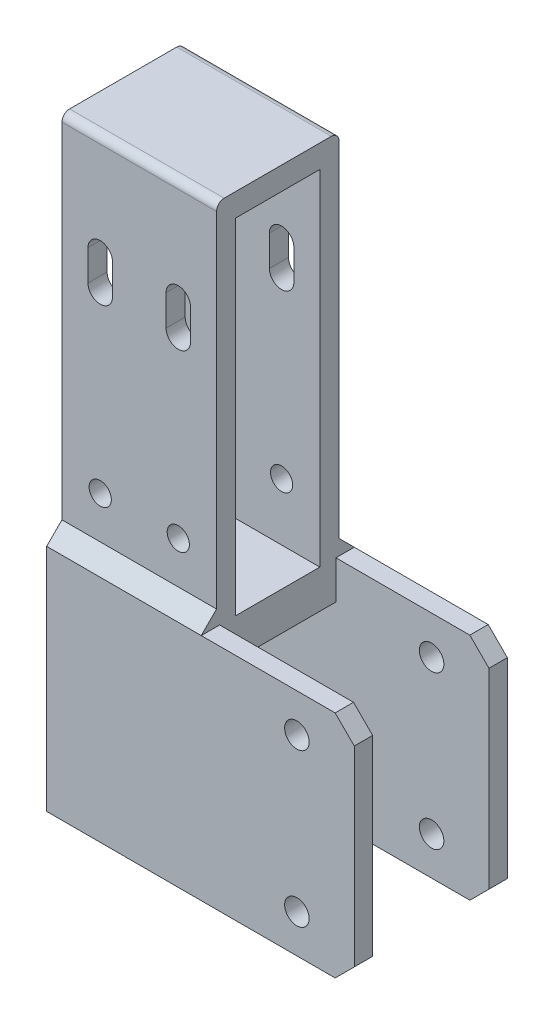
SolidWorks part; units mm, degrees
material "6061 合金"
ref_plane "前视基准面" through (0, 0, 0) normal (0, 0, 1) x (1, 0, 0)
ref_plane "上视基准面" through (0, 0, 0) normal (0, 1, 0) x (1, 0, 0)
ref_plane "右视基准面" through (0, 0, 0) normal (1, 0, 0) x (0, 0, -1)
sketch "草图1" plane through (0, 0, 0) normal (0, 1, 0) x (1, 0, 0)
  line L0 (-7.6, 0) -> (7.6, 0)
  line L1 (-7.6, 0) -> (-7.6, 15)
  line L2 (7.6, 0) -> (7.6, 15)
  dimension "D1" = 15.2
  dimension "D2" = 15
  dimension "D3" = 15
extrude "拉伸-薄壁1" add sketch "草图1" along normal blind 30 thin
sketch "草图2" plane through (0, 0, 2.5) normal (0, 0, 1) x (1, 0, 0)
  line L0 (-10.1, 0) -> (10.1, 0)
  line L1 (10.1, 0) -> (10.1, 50)
  line L2 (10.1, 50) -> (-10.1, 50)
  line L3 (-10.1, 50) -> (-10.1, 0)
  dimension "D1" = 50
extrude "凸台-拉伸1" add sketch "草图2" along normal blind 20
sketch "草图3" plane through (0, 50, 0) normal (0, 1, 0) x (1, 0, 0)
  line L0 (0, -2.5) -> (0, -22.5) construction
  line L1 (10.1, -2.5) -> (-10.1, -2.5) construction
  line L2 (10.1, -22.5) -> (-10.1, -22.5) construction
  line L3 (10.1, -22.5) -> (10.1, -2.5) construction
  line L4 (-10.1, -7) -> (10.1, -7)
  line L5 (-10.1, -7) -> (-10.1, -18)
  line L6 (-10.1, -18) -> (10.1, -18)
  line L7 (10.1, -7) -> (10.1, -18)
  line L8 (-10.1, -7) -> (10.1, -18) construction
  line L9 (-10.1, -18) -> (10.1, -7) construction
  point P6 (0, -12.5)
  dimension "D1" = 11
extrude "切除-拉伸1" cut sketch "草图3" against normal blind 20
sketch "草图4" plane through (10.1, 0, 0) normal (1, 0, 0) x (0, 0, -1)
  line L0 (-12.5, 30) -> (-12.5, 0) construction
  line L1 (-18, 30) -> (-7, 30) construction
  line L2 (-22.5, 0) -> (15, 0) construction
  line L4 (-7, 5) -> (-18, 5)
  line L5 (-7, 5) -> (-7, 25)
  line L6 (-7, 25) -> (-18, 25)
  line L7 (-18, 5) -> (-18, 25)
  line L8 (-7, 5) -> (-18, 25) construction
  line L9 (-7, 25) -> (-18, 5) construction
  point P6 (-12.5, 15)
  dimension "D1" = 11
  dimension "D2" = 20
extrude "切除-拉伸2" cut sketch "草图4" against normal up to next
sketch "草图5" plane through (0, 50, 0) normal (0, 1, 0) x (1, 0, 0)
  line L0 (-10.1, -2.5) -> (-10.1, -7) construction
  line L1 (-10.1, -7) -> (10.1, -7) construction
  line L2 (10.1, -7) -> (10.1, -2.5) construction
  line L3 (10.1, -2.5) -> (-10.1, -2.5) construction
  line L4 (10.1, -22.5) -> (10.1, -18) construction
  line L5 (10.1, -18) -> (-10.1, -18) construction
  line L6 (-10.1, -18) -> (-10.1, -22.5) construction
  line L7 (-10.1, -22.5) -> (10.1, -22.5) construction
  line L8 (-10.1, -2.5) -> (-10.1, -7)
  line L9 (-10.1, -7) -> (10.1, -7)
  line L10 (10.1, -7) -> (10.1, -2.5)
  line L11 (10.1, -2.5) -> (-10.1, -2.5)
  line L12 (10.1, -22.5) -> (10.1, -18)
  line L13 (10.1, -18) -> (-10.1, -18)
  line L14 (-10.1, -18) -> (-10.1, -22.5)
  line L15 (-10.1, -22.5) -> (10.1, -22.5)
extrude "凸台-拉伸2" add sketch "草图5" along normal blind 25
sketch "草图6" plane through (0, 0, 2.5) normal (0, 0, -1) x (-1, 0, 0)
  line L0 (5.1, 75) -> (5.1, 65) construction
  line L1 (-10.1, 75) -> (10.1, 75) construction
  line L2 (10.1, 75) -> (10.1, 30) construction
  line L3 (5.1, 65) -> (5.1, 37.5) construction
  line L4 (6.1, 37) -> (5.1, 43) construction
  point P10 (5.1, 37.5)
  dimension "D1" = 5
  dimension "D2" = 10
  dimension "D4" = 27.5
hole_wizard "M3.5 螺纹孔1" positions "3D草图1" profile "草图7" tap size "M3.5" standard "GB"
sketch3d "3D草图1"
  point P0 (-5.1, 37.5, 2.5)
sketch "草图7" plane through (-5.1, 37.5, 2.5) normal (1, 0, 0) x (0, 1, 0)
  line L0 (0, 0) -> (0, 40.8712)
  line L1 (0, 40.8712) -> (1.45, 40)
  line L2 (1.45, 40) -> (1.45, 0)
  line L5 (1.45, 0) -> (0, 0)
  line L10 (0, 40.8712) -> (-1.45, 40) construction
  line L11 (0, -6.35) -> (0, 107.95) construction
  dimension "螺纹孔钻头直径" = 2.9
  dimension "螺纹孔钻头深度" = 40
  dimension "导头角度" = 118
cosmetic thread "孔螺蚊线1" parameters "D1"=20, "D2"=3.5
sketch "草图8" plane through (0, 0, 2.5) normal (0, 0, -1) x (-1, 0, 0)
  line L0 (5.1, 37.5) -> (5.1, 62.5) construction
  line L1 (5.1, 60.5) -> (5.1, 64.5) construction
  line L2 (3.5, 60.5) -> (3.5, 64.5)
  line L3 (6.7, 60.5) -> (6.7, 64.5)
  arc A0 (3.5, 60.5) -> (6.7, 60.5) centre (5.1, 60.5) ccw
  arc A1 (6.7, 64.5) -> (3.5, 64.5) centre (5.1, 64.5) ccw
  point P5 (5.1, 62.5)
  dimension "D1" = 25
extrude "切除-拉伸4" cut sketch "草图8" against normal up to surface (20 mm away) up to face at (-3.65, 37.5, 22.5)
sketch "草图9" plane through (-7.6, 0, 0) normal (1, 0, 0) x (0, 0, -1)
  line L0 (15, 15) -> (0, 15) construction
  line L1 (15, 30) -> (15, 0) construction
  line L2 (0, 30) -> (0, 0) construction
  line L3 (7.5, 15) -> (7.5, 25) construction
  circle A0 centre (7.5, 25) radius 1.6
  circle A1 centre (7.5, 5) radius 1.6
  dimension "D2" = 3.2
  dimension "D1" = 10
extrude "切除-拉伸5" cut sketch "草图9" against normal up to next
mirror "镜向1" about plane through (0, 0, 0) normal (1, 0, 0) of "切除-拉伸4", "M3.5 螺纹孔1", "切除-拉伸5"
sketch "草图10" plane through (0, 75, 0) normal (0, 1, 0) x (1, 0, 0)
  line L0 (10.1, -2.5) -> (10.1, -22.5)
  line L1 (10.1, -22.5) -> (-10.1, -22.5)
  line L2 (-10.1, -22.5) -> (-10.1, -2.5)
  line L3 (-10.1, -2.5) -> (10.1, -2.5)
extrude "凸台-拉伸3" add sketch "草图10" along normal blind 3
sketch "草图11" plane through (0, 30, 0) normal (0, 1, 0) x (1, 0, 0)
  line L8 (10.1, -2.5) -> (10.1, 15)
  line L9 (10.1, 15) -> (7.6, 15)
  line L10 (7.6, 15) -> (7.6, 0)
  line L11 (7.6, 0) -> (-7.6, 0)
  line L12 (-7.6, 0) -> (-7.6, 15)
  line L13 (-7.6, 15) -> (-10.1, 15)
  line L14 (-10.1, 15) -> (-10.1, -2.5)
  line L15 (-10.1, -2.5) -> (10.1, -2.5)
  line L16 (10.1, -2.5) -> (10.1, 15)
  line L17 (10.1, 15) -> (7.6, 15)
  line L18 (7.6, 15) -> (7.6, 0)
  line L19 (7.6, 0) -> (-7.6, 0)
  line L20 (-7.6, 0) -> (-7.6, 15)
  line L21 (-7.6, 15) -> (-10.1, 15)
  line L22 (-10.1, 15) -> (-10.1, -2.5)
  line L23 (-10.1, -2.5) -> (10.1, -2.5)
  dimension "D1" = 0
extrude "切除-拉伸6" cut sketch "草图11" against normal up to next
sketch "草图12" plane through (0, 0, 22.5) normal (0, 0, 1) x (1, 0, 0)
  line L0 (10.1, 0) -> (10.1, 30)
  line L1 (10.1, 0) -> (10.1, 78) construction
  line L2 (10.1, 30) -> (-10.1, 30)
  line L3 (-10.1, 78) -> (-10.1, 0) construction
  line L4 (-10.1, 30) -> (-10.1, 0)
  line L5 (-10.1, 0) -> (10.1, 0)
  dimension "D1" = 30
extrude "凸台-拉伸4" add sketch "草图12" along normal blind 2
sketch "草图13" plane through (0, 0, 2.5) normal (0, 0, -1) x (-1, 0, 0)
  line L0 (-10.1, 0) -> (-10.1, 30)
  line L1 (-10.1, 0) -> (-10.1, 78) construction
  line L2 (-10.1, 30) -> (10.1, 30)
  line L3 (10.1, 78) -> (10.1, 0) construction
  line L4 (10.1, 30) -> (10.1, 0)
  line L5 (10.1, 0) -> (-10.1, 0)
  dimension "D1" = 30
extrude "凸台-拉伸5" add sketch "草图13" along normal blind 2
sketch "草图15" plane through (10.1, 0, 0) normal (1, 0, 0) x (0, 0, -1)
  line L0 (-12.5, 25) -> (-12.5, 5) construction
  line L1 (-7, 25) -> (-18, 25) construction
  line L2 (-18, 5) -> (-7, 5) construction
  line L4 (-20.1, 25) -> (-4.9, 25)
  line L5 (-20.1, 25) -> (-20.1, 5)
  line L6 (-20.1, 5) -> (-4.9, 5)
  line L7 (-4.9, 25) -> (-4.9, 5)
  line L8 (-20.1, 25) -> (-4.9, 5) construction
  line L9 (-20.1, 5) -> (-4.9, 25) construction
  point P6 (-12.5, 15)
  dimension "D1" = 15.2
extrude "切除-拉伸7" cut sketch "草图15" against normal up to next
sketch "草图16" plane through (10.1, 0, 0) normal (1, 0, 0) x (0, 0, -1)
  line L0 (-24.5, 0) -> (-24.5, 30)
  line L1 (-24.5, 30) -> (-20.1, 30)
  line L2 (-20.1, 30) -> (-20.1, 0)
  line L3 (-24.5, 0) -> (-0.5, 0) construction
  line L4 (-20.1, 0) -> (-24.5, 0)
  line L5 (-0.5, 30) -> (-0.5, 0)
  line L6 (-0.5, 0) -> (-5.9, 0)
  line L7 (-5.9, 0) -> (-5.9, 30)
  line L8 (-5.9, 30) -> (-0.5, 30)
extrude "凸台-拉伸6" add sketch "草图16" along normal blind 20
sketch "草图17" plane through (0, 0, 24.5) normal (0, 0, 1) x (1, 0, 0)
  line L0 (30.1, 15) -> (22.6, 15) construction
  line L1 (30.1, 30) -> (30.1, 0) construction
  line L2 (22.6, 15) -> (22.6, 25) construction
  circle A0 centre (22.6, 25) radius 1.6
  circle A1 centre (22.6, 5) radius 1.6
  dimension "D3" = 3.2
  dimension "D1" = 7.5
  dimension "D2" = 10
extrude "切除-拉伸8" cut sketch "草图17" against normal up to surface (24 mm away) up to face at (10, 15, 0.5)
chamfer "倒角1" distance 2.5 angle 45 4 edges at (30.1, 0, 22.3) (30.1, 0, 3.2) (30.1, 30, 3.2) (30.1, 30, 22.3)
sketch "草图18" plane through (0, 0, 0) normal (0, -1, 0) x (1, 0, 0)
  line L0 (27.6, 0.5) -> (-10.1, 0.5) construction
  line L1 (31.9046, -1) -> (-14.4046, -1)
  line L2 (31.9046, -1) -> (31.9046, 2)
  line L3 (31.9046, 2) -> (-14.4046, 2)
  line L4 (-14.4046, -1) -> (-14.4046, 2)
  line L5 (31.9046, -1) -> (-14.4046, 2) construction
  line L6 (31.9046, 2) -> (-14.4046, -1) construction
  point P0 (8.75, 0.5)
  dimension "D1" = 3
extrude "切除-拉伸9" cut sketch "草图18" against normal up to surface (78 mm away) up to face at (0, 78, 12.5)
sketch "草图20" plane through (0, 0, 4.9) normal (0, 0, 1) x (1, 0, 0)
  line L4 (-10.1, 25) -> (-10.1, 5)
  line L5 (-10.1, 5) -> (10.1, 5)
  line L6 (10.1, 5) -> (10.1, 25)
  line L7 (10.1, 25) -> (-10.1, 25)
  line L8 (-10.1, 25) -> (-10.1, 5)
  line L9 (-10.1, 5) -> (10.1, 5)
  line L10 (10.1, 5) -> (10.1, 25)
  line L11 (10.1, 25) -> (-10.1, 25)
  dimension "D1" = 0
extrude "凸台-拉伸7" add sketch "草图20" along normal up to surface (2.1 mm away) up to face at (0, 52.5, 7)
sketch "草图21" plane through (0, 0, 20.1) normal (0, 0, -1) x (-1, 0, 0)
  line L0 (10.1, 5) -> (10.1, 25) construction
  line L1 (10.1, 5) -> (-10.1, 5) construction
  line L2 (10.1, 25) -> (-10.1, 25) construction
  line L3 (10.1, 5) -> (10.1, 25)
  line L4 (10.1, 5) -> (-10.1, 5)
  line L5 (10.1, 25) -> (-10.1, 25)
  line L6 (-10.1, 25) -> (-10.1, 5)
extrude "凸台-拉伸8" add sketch "草图21" along normal up to surface (2.1 mm away) up to face at (0, 52.5, 18)
sketch "草图22" plane through (0, 30, 0) normal (0, 1, 0) x (1, 0, 0)
  line L0 (27.6, -2) -> (-10.1, -2) construction
  line L1 (31.8533, -1.5) -> (-14.3533, -1.5)
  line L2 (31.8533, -1.5) -> (31.8533, -2.5)
  line L3 (31.8533, -2.5) -> (-14.3533, -2.5)
  line L4 (-14.3533, -1.5) -> (-14.3533, -2.5)
  line L5 (31.8533, -1.5) -> (-14.3533, -2.5) construction
  line L6 (31.8533, -2.5) -> (-14.3533, -1.5) construction
  point P0 (8.75, -2)
  dimension "D1" = 1
extrude "切除-拉伸10" cut sketch "草图22" against normal up to surface (30 mm away) up to face at (14.8937, 0, 14.0125)
sketch "草图23" plane through (0, 30, 0) normal (0, 1, 0) x (1, 0, 0)
  line L0 (27.6, -24.5) -> (-10.1, -24.5) construction
  line L1 (30.2112, -26.5) -> (-12.7112, -26.5)
  line L2 (30.2112, -26.5) -> (30.2112, -22.5)
  line L3 (30.2112, -22.5) -> (-12.7112, -22.5)
  line L4 (-12.7112, -26.5) -> (-12.7112, -22.5)
  line L5 (30.2112, -26.5) -> (-12.7112, -22.5) construction
  line L6 (30.2112, -22.5) -> (-12.7112, -26.5) construction
  point P0 (8.75, -24.5)
  dimension "D1" = 4
extrude "切除-拉伸11" cut sketch "草图23" against normal up to surface (30 mm away) up to face at (14.8937, 0, 14.1375)
sketch "草图24" plane through (10.1, 0, 0) normal (1, 0, 0) x (0, 0, -1)
  line L0 (-22.5, 30) -> (-22.5, 78) construction
  line L1 (-24.5, 78) -> (-20.5, 78)
  line L2 (-24.5, 78) -> (-24.5, 30)
  line L3 (-24.5, 30) -> (-20.5, 30)
  line L4 (-20.5, 78) -> (-20.5, 30)
  line L5 (-24.5, 78) -> (-20.5, 30) construction
  line L6 (-24.5, 30) -> (-20.5, 78) construction
  line L7 (-20.1, 30) -> (-22.5, 30) construction
  line L8 (-12.5, 78) -> (-12.5, 63.3761) construction
  line L9 (-22.5, 78) -> (-2.5, 78) construction
  line L10 (-0.5, 30) -> (-4.5, 78) construction
  line L11 (-0.5, 78) -> (-4.5, 30) construction
  line L12 (-4.5, 78) -> (-4.5, 30)
  line L13 (-0.5, 30) -> (-4.5, 30)
  line L14 (-0.5, 78) -> (-0.5, 30)
  line L15 (-0.5, 78) -> (-4.5, 78)
  point P0 (-22.5, 54)
  point P17 (-2.5, 54)
  dimension "D1" = 4
extrude "切除-拉伸12" cut sketch "草图24" against normal up to next
sketch "草图25" plane through (10.1, 0, 0) normal (1, 0, 0) x (0, 0, -1)
  line L0 (-12.5, 5) -> (-12.5, 25) construction
  line L1 (-18, 5) -> (-7, 5) construction
  line L2 (-7, 25) -> (-18, 25) construction
  line L3 (-20.1, 0) -> (-20.1, 30) construction
  line L4 (-4.9, 5) -> (-20.1, 5)
  line L5 (-4.9, 5) -> (-4.9, 25)
  line L6 (-4.9, 25) -> (-20.1, 25)
  line L7 (-20.1, 5) -> (-20.1, 25)
  line L8 (-4.9, 5) -> (-20.1, 25) construction
  line L9 (-4.9, 25) -> (-20.1, 5) construction
  point P6 (-12.5, 15)
extrude "切除-拉伸13" cut sketch "草图25" against normal up to next
sketch "草图26" plane through (0, 0, 4.9) normal (0, 0, 1) x (1, 0, 0)
  line L4 (-10.1, 25) -> (-10.1, 5)
  line L5 (-10.1, 5) -> (10.1, 5)
  line L6 (10.1, 5) -> (10.1, 25)
  line L7 (10.1, 25) -> (-10.1, 25)
  line L8 (-10.1, 25) -> (-10.1, 5)
  line L9 (-10.1, 5) -> (10.1, 5)
  line L10 (10.1, 5) -> (10.1, 25)
  line L11 (10.1, 25) -> (-10.1, 25)
  dimension "D1" = 0
extrude "凸台-拉伸9" add sketch "草图26" along normal up to surface (1 mm away) up to face at (21, 5, 5.9)
chamfer "倒角2" distance 2 angle 45 2 edges at (0, 30, 4.5) (0, 30, 20.5)
fillet "圆角1" radius 1 2 edges at (0, 78, 20.5) (0, 78, 4.5)
sketch "草图27" plane through (0, 0, 5.9) normal (0, 0, 1) x (1, 0, 0)
  line L10 (10.1, 0) -> (27.6, 0)
  line L11 (27.6, 0) -> (30.1, 2.5)
  line L12 (30.1, 2.5) -> (30.1, 27.5)
  line L13 (30.1, 27.5) -> (27.6, 30)
  line L14 (27.6, 30) -> (10.1, 30)
  line L15 (10.1, 30) -> (10.1, 25)
  line L16 (10.1, 25) -> (-10.1, 25)
  line L17 (-10.1, 25) -> (-10.1, 5)
  line L18 (-10.1, 5) -> (10.1, 5)
  line L19 (10.1, 5) -> (10.1, 0)
  line L20 (10.1, 0) -> (27.6, 0)
  line L21 (27.6, 0) -> (30.1, 2.5)
  line L22 (30.1, 2.5) -> (30.1, 27.5)
  line L23 (30.1, 27.5) -> (27.6, 30)
  line L24 (27.6, 30) -> (10.1, 30)
  line L25 (10.1, 30) -> (10.1, 25)
  line L26 (10.1, 25) -> (-10.1, 25)
  line L27 (-10.1, 25) -> (-10.1, 5)
  line L28 (-10.1, 5) -> (10.1, 5)
  line L29 (10.1, 5) -> (10.1, 0)
  dimension "D1" = 0
extrude "切除-拉伸14" cut sketch "草图27" against normal blind 1
